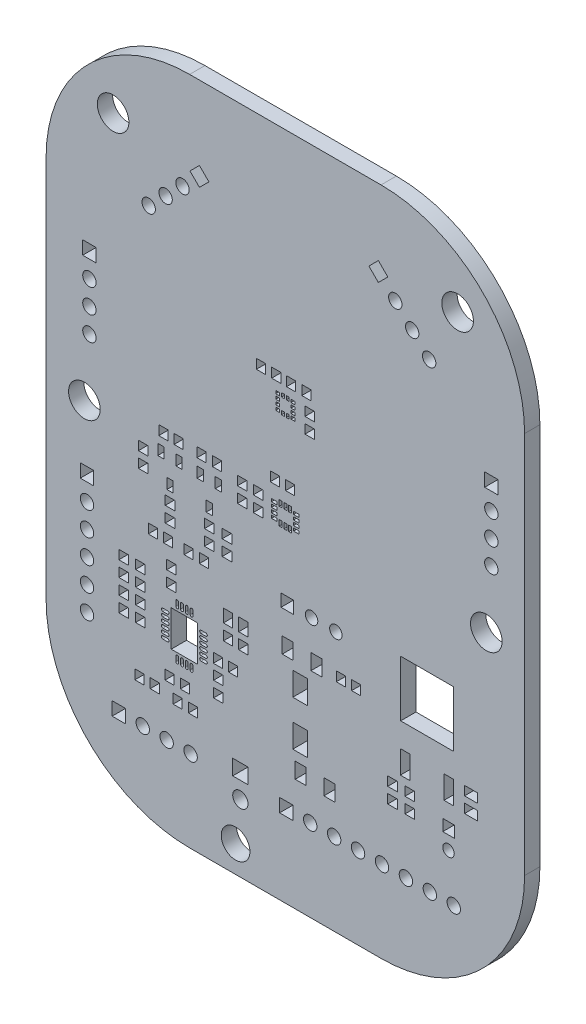
SolidWorks part; units mm, degrees
ref_plane "Plan de face" through (0, 0, 0) normal (0, 0, 1) x (1, 0, 0)
ref_plane "Plan de dessus" through (0, 0, 0) normal (0, 1, 0) x (1, 0, 0)
ref_plane "Plan de droite" through (0, 0, 0) normal (1, 0, 0) x (0, 0, -1)
sketch "Model" plane through (0, 0, 0) normal (0, 0, 1) x (1, 0, 0)
  line L0 (26, 44.4) -> (26, 44.1)
  line L1 (26, 44.1) -> (25.6, 44.1)
  line L2 (25.6, 44.1) -> (25.6, 44.4)
  line L3 (25.6, 44.4) -> (26, 44.4)
  line L4 (26, 44.9) -> (26, 44.6)
  line L5 (26, 44.6) -> (25.6, 44.6)
  line L6 (25.6, 44.6) -> (25.6, 44.9)
  line L7 (25.6, 44.9) -> (26, 44.9)
  line L8 (26, 45.4) -> (26, 45.1)
  line L9 (26, 45.1) -> (25.6, 45.1)
  line L10 (25.6, 45.1) -> (25.6, 45.4)
  line L11 (25.6, 45.4) -> (26, 45.4)
  line L12 (26, 45.9) -> (26, 45.6)
  line L13 (26, 45.6) -> (25.6, 45.6)
  line L14 (25.6, 45.6) -> (25.6, 45.9)
  line L15 (25.6, 45.9) -> (26, 45.9)
  line L16 (25.1, 46) -> (25.4, 46)
  line L17 (25.4, 46) -> (25.4, 45.6)
  line L18 (25.4, 45.6) -> (25.1, 45.6)
  line L19 (25.1, 45.6) -> (25.1, 46)
  line L20 (24.6, 46) -> (24.9, 46)
  line L21 (24.9, 46) -> (24.9, 45.6)
  line L22 (24.9, 45.6) -> (24.6, 45.6)
  line L23 (24.6, 45.6) -> (24.6, 46)
  line L24 (24.4, 45.9) -> (24.4, 45.6)
  line L25 (24.4, 45.6) -> (24, 45.6)
  line L26 (24, 45.6) -> (24, 45.9)
  line L27 (24, 45.9) -> (24.4, 45.9)
  line L28 (24.4, 45.4) -> (24.4, 45.1)
  line L29 (24.4, 45.1) -> (24, 45.1)
  line L30 (24, 45.1) -> (24, 45.4)
  line L31 (24, 45.4) -> (24.4, 45.4)
  line L32 (24.4, 44.9) -> (24.4, 44.6)
  line L33 (24.4, 44.6) -> (24, 44.6)
  line L34 (24, 44.6) -> (24, 44.9)
  line L35 (24, 44.9) -> (24.4, 44.9)
  line L36 (24.4, 44.4) -> (24.4, 44.1)
  line L37 (24.4, 44.1) -> (24, 44.1)
  line L38 (24, 44.1) -> (24, 44.4)
  line L39 (24, 44.4) -> (24.4, 44.4)
  line L40 (24.6, 44.4) -> (24.9, 44.4)
  line L41 (24.9, 44.4) -> (24.9, 44)
  line L42 (24.9, 44) -> (24.6, 44)
  line L43 (24.6, 44) -> (24.6, 44.4)
  line L44 (25.1, 44.4) -> (25.4, 44.4)
  line L45 (25.4, 44.4) -> (25.4, 44)
  line L46 (25.4, 44) -> (25.1, 44)
  line L47 (25.1, 44) -> (25.1, 44.4)
  line L48 (26.45, 34.4) -> (26.45, 34.1)
  line L49 (26.45, 34.1) -> (25.85, 34.1)
  line L50 (25.85, 34.1) -> (25.85, 34.4)
  line L51 (25.85, 34.4) -> (26.45, 34.4)
  line L52 (26.45, 34.9) -> (26.45, 34.6)
  line L53 (26.45, 34.6) -> (25.85, 34.6)
  line L54 (25.85, 34.6) -> (25.85, 34.9)
  line L55 (25.85, 34.9) -> (26.45, 34.9)
  line L56 (26.45, 35.4) -> (26.45, 35.1)
  line L57 (26.45, 35.1) -> (25.85, 35.1)
  line L58 (25.85, 35.1) -> (25.85, 35.4)
  line L59 (25.85, 35.4) -> (26.45, 35.4)
  line L60 (26.45, 35.9) -> (26.45, 35.6)
  line L61 (26.45, 35.6) -> (25.85, 35.6)
  line L62 (25.85, 35.6) -> (25.85, 35.9)
  line L63 (25.85, 35.9) -> (26.45, 35.9)
  line L64 (25.35, 36.2) -> (25.65, 36.2)
  line L65 (25.65, 36.2) -> (25.65, 35.6)
  line L66 (25.65, 35.6) -> (25.35, 35.6)
  line L67 (25.35, 35.6) -> (25.35, 36.2)
  line L68 (24.85, 36.2) -> (25.15, 36.2)
  line L69 (25.15, 36.2) -> (25.15, 35.6)
  line L70 (25.15, 35.6) -> (24.85, 35.6)
  line L71 (24.85, 35.6) -> (24.85, 36.2)
  line L72 (24.35, 36.2) -> (24.65, 36.2)
  line L73 (24.65, 36.2) -> (24.65, 35.6)
  line L74 (24.65, 35.6) -> (24.35, 35.6)
  line L75 (24.35, 35.6) -> (24.35, 36.2)
  line L76 (24.15, 35.9) -> (24.15, 35.6)
  line L77 (24.15, 35.6) -> (23.55, 35.6)
  line L78 (23.55, 35.6) -> (23.55, 35.9)
  line L79 (23.55, 35.9) -> (24.15, 35.9)
  line L80 (24.15, 35.4) -> (24.15, 35.1)
  line L81 (24.15, 35.1) -> (23.55, 35.1)
  line L82 (23.55, 35.1) -> (23.55, 35.4)
  line L83 (23.55, 35.4) -> (24.15, 35.4)
  line L84 (24.15, 34.9) -> (24.15, 34.6)
  line L85 (24.15, 34.6) -> (23.55, 34.6)
  line L86 (23.55, 34.6) -> (23.55, 34.9)
  line L87 (23.55, 34.9) -> (24.15, 34.9)
  line L88 (24.15, 34.4) -> (24.15, 34.1)
  line L89 (24.15, 34.1) -> (23.55, 34.1)
  line L90 (23.55, 34.1) -> (23.55, 34.4)
  line L91 (23.55, 34.4) -> (24.15, 34.4)
  line L92 (24.35, 34.4) -> (24.65, 34.4)
  line L93 (24.65, 34.4) -> (24.65, 33.8)
  line L94 (24.65, 33.8) -> (24.35, 33.8)
  line L95 (24.35, 33.8) -> (24.35, 34.4)
  line L96 (24.85, 34.4) -> (25.15, 34.4)
  line L97 (25.15, 34.4) -> (25.15, 33.8)
  line L98 (25.15, 33.8) -> (24.85, 33.8)
  line L99 (24.85, 33.8) -> (24.85, 34.4)
  line L100 (25.35, 34.4) -> (25.65, 34.4)
  line L101 (25.65, 34.4) -> (25.65, 33.8)
  line L102 (25.65, 33.8) -> (25.35, 33.8)
  line L103 (25.35, 33.8) -> (25.35, 34.4)
  line L104 (20.125, 23.475) -> (21.075, 23.475)
  line L105 (21.075, 23.475) -> (21.075, 22.125)
  line L106 (21.075, 22.125) -> (20.125, 22.125)
  line L107 (20.125, 22.125) -> (20.125, 23.475)
  line L108 (18.525, 23.475) -> (19.475, 23.475)
  line L109 (19.475, 23.475) -> (19.475, 22.125)
  line L110 (19.475, 22.125) -> (18.525, 22.125)
  line L111 (18.525, 22.125) -> (18.525, 23.475)
  line L112 (16.2, 17.8) -> (16.7, 17.8)
  line L113 (16.7, 17.5) -> (16.2, 17.5)
  line L114 (16.2, 18.3) -> (16.7, 18.3)
  line L115 (16.7, 18) -> (16.2, 18)
  line L116 (16.2, 18.8) -> (16.7, 18.8)
  line L117 (16.7, 18.5) -> (16.2, 18.5)
  line L118 (16.2, 19.3) -> (16.7, 19.3)
  line L119 (16.7, 19) -> (16.2, 19)
  line L120 (16.2, 19.8) -> (16.7, 19.8)
  line L121 (16.7, 19.5) -> (16.2, 19.5)
  line L122 (16.2, 20.3) -> (16.7, 20.3)
  line L123 (16.7, 20) -> (16.2, 20)
  line L124 (15.05, 21.15) -> (15.05, 21.65)
  line L125 (15.35, 21.65) -> (15.35, 21.15)
  line L126 (14.55, 21.15) -> (14.55, 21.65)
  line L127 (14.85, 21.65) -> (14.85, 21.15)
  line L128 (14.05, 21.15) -> (14.05, 21.65)
  line L129 (14.35, 21.65) -> (14.35, 21.15)
  line L130 (13.55, 21.15) -> (13.55, 21.65)
  line L131 (13.85, 21.65) -> (13.85, 21.15)
  line L132 (12.2, 20.3) -> (12.7, 20.3)
  line L133 (12.7, 20) -> (12.2, 20)
  line L134 (12.2, 19.8) -> (12.7, 19.8)
  line L135 (12.7, 19.5) -> (12.2, 19.5)
  line L136 (12.2, 19.3) -> (12.7, 19.3)
  line L137 (12.7, 19) -> (12.2, 19)
  line L138 (12.2, 18.8) -> (12.7, 18.8)
  line L139 (12.7, 18.5) -> (12.2, 18.5)
  line L140 (12.2, 18.3) -> (12.7, 18.3)
  line L141 (12.7, 18) -> (12.2, 18)
  line L142 (12.2, 17.8) -> (12.7, 17.8)
  line L143 (12.7, 17.5) -> (12.2, 17.5)
  line L144 (13.55, 16.15) -> (13.55, 16.65)
  line L145 (13.85, 16.65) -> (13.85, 16.15)
  line L146 (14.05, 16.15) -> (14.05, 16.65)
  line L147 (14.35, 16.65) -> (14.35, 16.15)
  line L148 (14.55, 16.15) -> (14.55, 16.65)
  line L149 (14.85, 16.65) -> (14.85, 16.15)
  line L150 (15.05, 16.15) -> (15.05, 16.65)
  line L151 (15.35, 16.65) -> (15.35, 16.15)
  line L152 (15.825, 20.775) -> (15.825, 17.025)
  line L153 (15.825, 17.025) -> (13.075, 17.025)
  line L154 (13.075, 17.025) -> (13.075, 20.775)
  line L155 (13.075, 20.775) -> (15.825, 20.775)
  line L156 (13.575, 34.95) -> (14.225, 34.95)
  line L157 (14.225, 34.95) -> (14.225, 33.85)
  line L158 (14.225, 33.85) -> (13.575, 33.85)
  line L159 (13.575, 33.85) -> (13.575, 34.95)
  line L160 (11.675, 34.95) -> (12.325, 34.95)
  line L161 (12.325, 34.95) -> (12.325, 33.85)
  line L162 (12.325, 33.85) -> (11.675, 33.85)
  line L163 (11.675, 33.85) -> (11.675, 34.95)
  line L164 (12.625, 32.35) -> (13.275, 32.35)
  line L165 (13.275, 32.35) -> (13.275, 31.25)
  line L166 (13.275, 31.25) -> (12.625, 31.25)
  line L167 (12.625, 31.25) -> (12.625, 32.35)
  line L168 (17.675, 34.95) -> (18.325, 34.95)
  line L169 (18.325, 34.95) -> (18.325, 33.85)
  line L170 (18.325, 33.85) -> (17.675, 33.85)
  line L171 (17.675, 33.85) -> (17.675, 34.95)
  line L172 (15.775, 34.95) -> (16.425, 34.95)
  line L173 (16.425, 34.95) -> (16.425, 33.85)
  line L174 (16.425, 33.85) -> (15.775, 33.85)
  line L175 (15.775, 33.85) -> (15.775, 34.95)
  line L176 (16.725, 32.35) -> (17.375, 32.35)
  line L177 (17.375, 32.35) -> (17.375, 31.25)
  line L178 (17.375, 31.25) -> (16.725, 31.25)
  line L179 (16.725, 31.25) -> (16.725, 32.35)
  line L180 (43.725, 19.075) -> (43.725, 20.025)
  line L181 (43.725, 20.025) -> (45.075, 20.025)
  line L182 (45.075, 20.025) -> (45.075, 19.075)
  line L183 (45.075, 19.075) -> (43.725, 19.075)
  line L184 (43.725, 17.475) -> (43.725, 18.425)
  line L185 (43.725, 18.425) -> (45.075, 18.425)
  line L186 (45.075, 18.425) -> (45.075, 17.475)
  line L187 (45.075, 17.475) -> (43.725, 17.475)
  line L188 (41.45, 15.9) -> (42.65, 15.9)
  line L189 (42.65, 15.9) -> (42.65, 14.7)
  line L190 (42.65, 14.7) -> (41.45, 14.7)
  line L191 (41.45, 14.7) -> (41.45, 15.9)
  line L192 (41.45, 15.9) -> (42.65, 15.9)
  line L193 (42.65, 15.9) -> (42.65, 14.7)
  line L194 (42.65, 14.7) -> (41.45, 14.7)
  line L195 (41.45, 14.7) -> (41.45, 15.9)
  line L196 (38.02, 17.6) -> (37.02, 17.6)
  line L197 (37.02, 17.6) -> (37.02, 20)
  line L198 (37.02, 20) -> (38.02, 20)
  line L199 (38.02, 20) -> (38.02, 17.6)
  line L200 (42.58, 17.6) -> (41.58, 17.6)
  line L201 (41.58, 17.6) -> (41.58, 20)
  line L202 (41.58, 20) -> (42.58, 20)
  line L203 (42.58, 20) -> (42.58, 17.6)
  line L204 (42.55, 22.525) -> (37.05, 22.525)
  line L205 (37.05, 22.525) -> (37.05, 28.375)
  line L206 (37.05, 28.375) -> (42.55, 28.375)
  line L207 (42.55, 28.375) -> (42.55, 22.525)
  line L208 (37.5, 15.925) -> (37.5, 16.875)
  line L209 (37.5, 16.875) -> (38.5, 16.875)
  line L210 (38.5, 16.875) -> (38.5, 15.925)
  line L211 (38.5, 15.925) -> (37.5, 15.925)
  line L212 (37.5, 14.325) -> (37.5, 15.275)
  line L213 (37.5, 15.275) -> (38.5, 15.275)
  line L214 (38.5, 15.275) -> (38.5, 14.325)
  line L215 (38.5, 14.325) -> (37.5, 14.325)
  line L216 (22.925, 46.8) -> (21.975, 46.8)
  line L217 (21.975, 46.8) -> (21.975, 47.8)
  line L218 (21.975, 47.8) -> (22.925, 47.8)
  line L219 (22.925, 47.8) -> (22.925, 46.8)
  line L220 (24.525, 46.8) -> (23.575, 46.8)
  line L221 (23.575, 46.8) -> (23.575, 47.8)
  line L222 (23.575, 47.8) -> (24.525, 47.8)
  line L223 (24.525, 47.8) -> (24.525, 46.8)
  line L224 (26.725, 47.8) -> (27.675, 47.8)
  line L225 (27.675, 47.8) -> (27.675, 46.8)
  line L226 (27.675, 46.8) -> (26.725, 46.8)
  line L227 (26.725, 46.8) -> (26.725, 47.8)
  line L228 (25.125, 47.8) -> (26.075, 47.8)
  line L229 (26.075, 47.8) -> (26.075, 46.8)
  line L230 (26.075, 46.8) -> (25.125, 46.8)
  line L231 (25.125, 46.8) -> (25.125, 47.8)
  line L232 (28.05, 44.425) -> (28.05, 43.475)
  line L233 (28.05, 43.475) -> (27.05, 43.475)
  line L234 (27.05, 43.475) -> (27.05, 44.425)
  line L235 (27.05, 44.425) -> (28.05, 44.425)
  line L236 (28.05, 46.025) -> (28.05, 45.075)
  line L237 (28.05, 45.075) -> (27.05, 45.075)
  line L238 (27.05, 45.075) -> (27.05, 46.025)
  line L239 (27.05, 46.025) -> (28.05, 46.025)
  line L240 (24.375, 37.35) -> (23.425, 37.35)
  line L241 (23.425, 37.35) -> (23.425, 38.35)
  line L242 (23.425, 38.35) -> (24.375, 38.35)
  line L243 (24.375, 38.35) -> (24.375, 37.35)
  line L244 (25.975, 37.35) -> (25.025, 37.35)
  line L245 (25.025, 37.35) -> (25.025, 38.35)
  line L246 (25.025, 38.35) -> (25.975, 38.35)
  line L247 (25.975, 38.35) -> (25.975, 37.35)
  line L248 (21, 34.625) -> (21, 33.675)
  line L249 (21, 33.675) -> (20, 33.675)
  line L250 (20, 33.675) -> (20, 34.625)
  line L251 (20, 34.625) -> (21, 34.625)
  line L252 (21, 36.225) -> (21, 35.275)
  line L253 (21, 35.275) -> (20, 35.275)
  line L254 (20, 35.275) -> (20, 36.225)
  line L255 (20, 36.225) -> (21, 36.225)
  line L256 (22.65, 34.625) -> (22.65, 33.675)
  line L257 (22.65, 33.675) -> (21.65, 33.675)
  line L258 (21.65, 33.675) -> (21.65, 34.625)
  line L259 (21.65, 34.625) -> (22.65, 34.625)
  line L260 (22.65, 36.225) -> (22.65, 35.275)
  line L261 (22.65, 35.275) -> (21.65, 35.275)
  line L262 (21.65, 35.275) -> (21.65, 36.225)
  line L263 (21.65, 36.225) -> (22.65, 36.225)
  line L264 (19.475, 20.5) -> (18.525, 20.5)
  line L265 (18.525, 20.5) -> (18.525, 21.5)
  line L266 (18.525, 21.5) -> (19.475, 21.5)
  line L267 (19.475, 21.5) -> (19.475, 20.5)
  line L268 (21.075, 20.5) -> (20.125, 20.5)
  line L269 (20.125, 20.5) -> (20.125, 21.5)
  line L270 (20.125, 21.5) -> (21.075, 21.5)
  line L271 (21.075, 21.5) -> (21.075, 20.5)
  line L272 (14.025, 14.9) -> (14.975, 14.9)
  line L273 (14.975, 14.9) -> (14.975, 13.9)
  line L274 (14.975, 13.9) -> (14.025, 13.9)
  line L275 (14.025, 13.9) -> (14.025, 14.9)
  line L276 (12.425, 14.9) -> (13.375, 14.9)
  line L277 (13.375, 14.9) -> (13.375, 13.9)
  line L278 (13.375, 13.9) -> (12.425, 13.9)
  line L279 (12.425, 13.9) -> (12.425, 14.9)
  line L280 (10.875, 13.35) -> (11.825, 13.35)
  line L281 (11.825, 13.35) -> (11.825, 12.35)
  line L282 (11.825, 12.35) -> (10.875, 12.35)
  line L283 (10.875, 12.35) -> (10.875, 13.35)
  line L284 (9.275, 13.35) -> (10.225, 13.35)
  line L285 (10.225, 13.35) -> (10.225, 12.35)
  line L286 (10.225, 12.35) -> (9.275, 12.35)
  line L287 (9.275, 12.35) -> (9.275, 13.35)
  line L288 (12.6, 23.975) -> (12.6, 24.925)
  line L289 (12.6, 24.925) -> (13.6, 24.925)
  line L290 (13.6, 24.925) -> (13.6, 23.975)
  line L291 (13.6, 23.975) -> (12.6, 23.975)
  line L292 (12.6, 22.375) -> (12.6, 23.325)
  line L293 (12.6, 23.325) -> (13.6, 23.325)
  line L294 (13.6, 23.325) -> (13.6, 22.375)
  line L295 (13.6, 22.375) -> (12.6, 22.375)
  line L296 (19.075, 18.95) -> (20.025, 18.95)
  line L297 (20.025, 18.95) -> (20.025, 17.95)
  line L298 (20.025, 17.95) -> (19.075, 17.95)
  line L299 (19.075, 17.95) -> (19.075, 18.95)
  line L300 (17.475, 18.95) -> (18.425, 18.95)
  line L301 (18.425, 18.95) -> (18.425, 17.95)
  line L302 (18.425, 17.95) -> (17.475, 17.95)
  line L303 (17.475, 17.95) -> (17.475, 18.95)
  line L304 (18.5, 15.775) -> (18.5, 14.825)
  line L305 (18.5, 14.825) -> (17.5, 14.825)
  line L306 (17.5, 14.825) -> (17.5, 15.775)
  line L307 (17.5, 15.775) -> (18.5, 15.775)
  line L308 (18.5, 17.375) -> (18.5, 16.425)
  line L309 (18.5, 16.425) -> (17.5, 16.425)
  line L310 (17.5, 16.425) -> (17.5, 17.375)
  line L311 (17.5, 17.375) -> (18.5, 17.375)
  line L312 (14.875, 13.15) -> (15.825, 13.15)
  line L313 (15.825, 13.15) -> (15.825, 12.15)
  line L314 (15.825, 12.15) -> (14.875, 12.15)
  line L315 (14.875, 12.15) -> (14.875, 13.15)
  line L316 (13.275, 13.15) -> (14.225, 13.15)
  line L317 (14.225, 13.15) -> (14.225, 12.15)
  line L318 (14.225, 12.15) -> (13.275, 12.15)
  line L319 (13.275, 12.15) -> (13.275, 13.15)
  line L320 (8.6, 18.525) -> (8.6, 17.575)
  line L321 (8.6, 17.575) -> (7.6, 17.575)
  line L322 (7.6, 17.575) -> (7.6, 18.525)
  line L323 (7.6, 18.525) -> (8.6, 18.525)
  line L324 (8.6, 20.125) -> (8.6, 19.175)
  line L325 (8.6, 19.175) -> (7.6, 19.175)
  line L326 (7.6, 19.175) -> (7.6, 20.125)
  line L327 (7.6, 20.125) -> (8.6, 20.125)
  line L328 (10.35, 18.525) -> (10.35, 17.575)
  line L329 (10.35, 17.575) -> (9.35, 17.575)
  line L330 (9.35, 17.575) -> (9.35, 18.525)
  line L331 (9.35, 18.525) -> (10.35, 18.525)
  line L332 (10.35, 20.125) -> (10.35, 19.175)
  line L333 (10.35, 19.175) -> (9.35, 19.175)
  line L334 (9.35, 19.175) -> (9.35, 20.125)
  line L335 (9.35, 20.125) -> (10.35, 20.125)
  line L336 (8.6, 21.725) -> (8.6, 20.775)
  line L337 (8.6, 20.775) -> (7.6, 20.775)
  line L338 (7.6, 20.775) -> (7.6, 21.725)
  line L339 (7.6, 21.725) -> (8.6, 21.725)
  line L340 (8.6, 23.325) -> (8.6, 22.375)
  line L341 (8.6, 22.375) -> (7.6, 22.375)
  line L342 (7.6, 22.375) -> (7.6, 23.325)
  line L343 (7.6, 23.325) -> (8.6, 23.325)
  line L344 (10.35, 21.725) -> (10.35, 20.775)
  line L345 (10.35, 20.775) -> (9.35, 20.775)
  line L346 (9.35, 20.775) -> (9.35, 21.725)
  line L347 (9.35, 21.725) -> (10.35, 21.725)
  line L348 (10.35, 23.325) -> (10.35, 22.375)
  line L349 (10.35, 22.375) -> (9.35, 22.375)
  line L350 (9.35, 22.375) -> (9.35, 23.325)
  line L351 (9.35, 23.325) -> (10.35, 23.325)
  line L352 (15.375, 26.25) -> (14.425, 26.25)
  line L353 (14.425, 26.25) -> (14.425, 27.25)
  line L354 (14.425, 27.25) -> (15.375, 27.25)
  line L355 (15.375, 27.25) -> (15.375, 26.25)
  line L356 (16.975, 26.25) -> (16.025, 26.25)
  line L357 (16.025, 26.25) -> (16.025, 27.25)
  line L358 (16.025, 27.25) -> (16.975, 27.25)
  line L359 (16.975, 27.25) -> (16.975, 26.25)
  line L360 (11.625, 26.25) -> (10.675, 26.25)
  line L361 (10.675, 26.25) -> (10.675, 27.25)
  line L362 (10.675, 27.25) -> (11.625, 27.25)
  line L363 (11.625, 27.25) -> (11.625, 26.25)
  line L364 (13.225, 26.25) -> (12.275, 26.25)
  line L365 (12.275, 26.25) -> (12.275, 27.25)
  line L366 (12.275, 27.25) -> (13.225, 27.25)
  line L367 (13.225, 27.25) -> (13.225, 26.25)
  line L368 (10.65, 32.625) -> (10.65, 31.675)
  line L369 (10.65, 31.675) -> (9.65, 31.675)
  line L370 (9.65, 31.675) -> (9.65, 32.625)
  line L371 (9.65, 32.625) -> (10.65, 32.625)
  line L372 (10.65, 34.225) -> (10.65, 33.275)
  line L373 (10.65, 33.275) -> (9.65, 33.275)
  line L374 (9.65, 33.275) -> (9.65, 34.225)
  line L375 (9.65, 34.225) -> (10.65, 34.225)
  line L376 (13.375, 36.7) -> (14.325, 36.7)
  line L377 (14.325, 36.7) -> (14.325, 35.7)
  line L378 (14.325, 35.7) -> (13.375, 35.7)
  line L379 (13.375, 35.7) -> (13.375, 36.7)
  line L380 (11.775, 36.7) -> (12.725, 36.7)
  line L381 (12.725, 36.7) -> (12.725, 35.7)
  line L382 (12.725, 35.7) -> (11.775, 35.7)
  line L383 (11.775, 35.7) -> (11.775, 36.7)
  line L384 (13.45, 29.075) -> (13.45, 28.125)
  line L385 (13.45, 28.125) -> (12.45, 28.125)
  line L386 (12.45, 28.125) -> (12.45, 29.075)
  line L387 (12.45, 29.075) -> (13.45, 29.075)
  line L388 (13.45, 30.675) -> (13.45, 29.725)
  line L389 (13.45, 29.725) -> (12.45, 29.725)
  line L390 (12.45, 29.725) -> (12.45, 30.675)
  line L391 (12.45, 30.675) -> (13.45, 30.675)
  line L392 (17.375, 36.7) -> (18.325, 36.7)
  line L393 (18.325, 36.7) -> (18.325, 35.7)
  line L394 (18.325, 35.7) -> (17.375, 35.7)
  line L395 (17.375, 35.7) -> (17.375, 36.7)
  line L396 (15.775, 36.7) -> (16.725, 36.7)
  line L397 (16.725, 36.7) -> (16.725, 35.7)
  line L398 (16.725, 35.7) -> (15.775, 35.7)
  line L399 (15.775, 35.7) -> (15.775, 36.7)
  line L400 (17.55, 29.025) -> (17.55, 28.075)
  line L401 (17.55, 28.075) -> (16.55, 28.075)
  line L402 (16.55, 28.075) -> (16.55, 29.025)
  line L403 (16.55, 29.025) -> (17.55, 29.025)
  line L404 (17.55, 30.625) -> (17.55, 29.675)
  line L405 (17.55, 29.675) -> (16.55, 29.675)
  line L406 (16.55, 29.675) -> (16.55, 30.625)
  line L407 (16.55, 30.625) -> (17.55, 30.625)
  line L408 (36.7, 15.275) -> (36.7, 14.325)
  line L409 (36.7, 14.325) -> (35.7, 14.325)
  line L410 (35.7, 14.325) -> (35.7, 15.275)
  line L411 (35.7, 15.275) -> (36.7, 15.275)
  line L412 (36.7, 16.875) -> (36.7, 15.925)
  line L413 (36.7, 15.925) -> (35.7, 15.925)
  line L414 (35.7, 15.925) -> (35.7, 16.875)
  line L415 (35.7, 16.875) -> (36.7, 16.875)
  line L416 (31.275, 22.7) -> (30.325, 22.7)
  line L417 (30.325, 22.7) -> (30.325, 23.7)
  line L418 (30.325, 23.7) -> (31.275, 23.7)
  line L419 (31.275, 23.7) -> (31.275, 22.7)
  line L420 (32.875, 22.7) -> (31.925, 22.7)
  line L421 (31.925, 22.7) -> (31.925, 23.7)
  line L422 (31.925, 23.7) -> (32.875, 23.7)
  line L423 (32.875, 23.7) -> (32.875, 22.7)
  line L424 (19.4, 29.025) -> (19.4, 28.075)
  line L425 (19.4, 28.075) -> (18.4, 28.075)
  line L426 (18.4, 28.075) -> (18.4, 29.025)
  line L427 (18.4, 29.025) -> (19.4, 29.025)
  line L428 (19.4, 30.625) -> (19.4, 29.675)
  line L429 (19.4, 29.675) -> (18.4, 29.675)
  line L430 (18.4, 29.675) -> (18.4, 30.625)
  line L431 (18.4, 30.625) -> (19.4, 30.625)
  line L432 (27.675, 24.025) -> (28.825, 24.025)
  line L433 (28.825, 24.025) -> (28.825, 22.375)
  line L434 (28.825, 22.375) -> (27.675, 22.375)
  line L435 (27.675, 22.375) -> (27.675, 24.025)
  line L436 (24.675, 24.025) -> (25.825, 24.025)
  line L437 (25.825, 24.025) -> (25.825, 22.375)
  line L438 (25.825, 22.375) -> (24.675, 22.375)
  line L439 (24.675, 22.375) -> (24.675, 24.025)
  line L440 (29.025, 13.375) -> (30.175, 13.375)
  line L441 (30.175, 13.375) -> (30.175, 11.725)
  line L442 (30.175, 11.725) -> (29.025, 11.725)
  line L443 (29.025, 11.725) -> (29.025, 13.375)
  line L444 (26.025, 13.375) -> (27.175, 13.375)
  line L445 (27.175, 13.375) -> (27.175, 11.725)
  line L446 (27.175, 11.725) -> (26.025, 11.725)
  line L447 (26.025, 11.725) -> (26.025, 13.375)
  line L448 (27.325, 14.325) -> (25.775, 14.325)
  line L449 (25.775, 14.325) -> (25.775, 16.775)
  line L450 (25.775, 16.775) -> (27.325, 16.775)
  line L451 (27.325, 16.775) -> (27.325, 14.325)
  line L452 (27.325, 19.025) -> (25.775, 19.025)
  line L453 (25.775, 19.025) -> (25.775, 21.475)
  line L454 (25.775, 21.475) -> (27.325, 21.475)
  line L455 (27.325, 21.475) -> (27.325, 19.025)
  line L456 (45.825, 49.45) -> (47.225, 49.45)
  line L457 (47.225, 49.45) -> (47.225, 48.05)
  line L458 (47.225, 48.05) -> (45.825, 48.05)
  line L459 (45.825, 48.05) -> (45.825, 49.45)
  line L460 (45.825, 49.45) -> (47.225, 49.45)
  line L461 (47.225, 49.45) -> (47.225, 48.05)
  line L462 (47.225, 48.05) -> (45.825, 48.05)
  line L463 (45.825, 48.05) -> (45.825, 49.45)
  line L464 (33.7296, 62.0228) -> (34.7195, 63.0127)
  line L465 (34.7195, 63.0127) -> (35.7094, 62.0228)
  line L466 (35.7094, 62.0228) -> (34.7195, 61.0329)
  line L467 (34.7195, 61.0329) -> (33.7296, 62.0228)
  line L468 (33.7296, 62.0228) -> (34.7195, 63.0127)
  line L469 (34.7195, 63.0127) -> (35.7094, 62.0228)
  line L470 (35.7094, 62.0228) -> (34.7195, 61.0329)
  line L471 (34.7195, 61.0329) -> (33.7296, 62.0228)
  line L472 (16.0228, 62.2703) -> (17.0127, 61.2804)
  line L473 (17.0127, 61.2804) -> (16.0228, 60.2905)
  line L474 (16.0228, 60.2905) -> (15.0329, 61.2804)
  line L475 (15.0329, 61.2804) -> (16.0228, 62.2703)
  line L476 (16.0228, 62.2703) -> (17.0127, 61.2804)
  line L477 (17.0127, 61.2804) -> (16.0228, 60.2905)
  line L478 (16.0228, 60.2905) -> (15.0329, 61.2804)
  line L479 (15.0329, 61.2804) -> (16.0228, 62.2703)
  line L480 (3.825, 49.45) -> (5.225, 49.45)
  line L481 (5.225, 49.45) -> (5.225, 48.05)
  line L482 (5.225, 48.05) -> (3.825, 48.05)
  line L483 (3.825, 48.05) -> (3.825, 49.45)
  line L484 (3.825, 49.45) -> (5.225, 49.45)
  line L485 (5.225, 49.45) -> (5.225, 48.05)
  line L486 (5.225, 48.05) -> (3.825, 48.05)
  line L487 (3.825, 48.05) -> (3.825, 49.45)
  line L488 (6.9, 7.875) -> (6.9, 9.275)
  line L489 (6.9, 9.275) -> (8.3, 9.275)
  line L490 (8.3, 9.275) -> (8.3, 7.875)
  line L491 (8.3, 7.875) -> (6.9, 7.875)
  line L492 (6.9, 7.875) -> (6.9, 9.275)
  line L493 (6.9, 9.275) -> (8.3, 9.275)
  line L494 (8.3, 9.275) -> (8.3, 7.875)
  line L495 (8.3, 7.875) -> (6.9, 7.875)
  line L496 (19.5, 10.37) -> (21.1, 10.37)
  line L497 (21.1, 10.37) -> (21.1, 8.77)
  line L498 (21.1, 8.77) -> (19.5, 8.77)
  line L499 (19.5, 8.77) -> (19.5, 10.37)
  line L500 (19.5, 10.37) -> (21.1, 10.37)
  line L501 (21.1, 10.37) -> (21.1, 8.77)
  line L502 (21.1, 8.77) -> (19.5, 8.77)
  line L503 (19.5, 8.77) -> (19.5, 10.37)
  line L504 (24.4, 7.875) -> (24.4, 9.275)
  line L505 (24.4, 9.275) -> (25.8, 9.275)
  line L506 (25.8, 9.275) -> (25.8, 7.875)
  line L507 (25.8, 7.875) -> (24.4, 7.875)
  line L508 (24.4, 7.875) -> (24.4, 9.275)
  line L509 (24.4, 9.275) -> (25.8, 9.275)
  line L510 (25.8, 9.275) -> (25.8, 7.875)
  line L511 (25.8, 7.875) -> (24.4, 7.875)
  line L512 (3.575, 29.15) -> (4.975, 29.15)
  line L513 (4.975, 29.15) -> (4.975, 27.75)
  line L514 (4.975, 27.75) -> (3.575, 27.75)
  line L515 (3.575, 27.75) -> (3.575, 29.15)
  line L516 (3.575, 29.15) -> (4.975, 29.15)
  line L517 (4.975, 29.15) -> (4.975, 27.75)
  line L518 (4.975, 27.75) -> (3.575, 27.75)
  line L519 (3.575, 27.75) -> (3.575, 29.15)
  line L520 (24.55, 26.55) -> (24.55, 27.85)
  line L521 (24.55, 27.85) -> (25.85, 27.85)
  line L522 (25.85, 27.85) -> (25.85, 26.55)
  line L523 (25.85, 26.55) -> (24.55, 26.55)
  line L524 (24.55, 26.55) -> (24.55, 27.85)
  line L525 (24.55, 27.85) -> (25.85, 27.85)
  line L526 (25.85, 27.85) -> (25.85, 26.55)
  line L527 (25.85, 26.55) -> (24.55, 26.55)
  line L528 (15, 0) -> (35, 0)
  line L529 (50, 15) -> (50, 55)
  line L530 (35, 70) -> (15, 70)
  line L531 (0, 55) -> (0, 15)
  circle A0 centre (4, 35) radius 1.651
  circle A1 centre (4, 35) radius 1.651
  circle A2 centre (7, 62.5) radius 1.651
  circle A3 centre (7, 62.5) radius 1.651
  circle A4 centre (46, 35) radius 1.651
  circle A5 centre (46, 35) radius 1.651
  circle A6 centre (43, 62.5) radius 1.651
  circle A7 centre (43, 62.5) radius 1.651
  circle A8 centre (42.05, 13.3) radius 0.6
  circle A9 centre (42.05, 13.3) radius 0.6
  circle A10 centre (19.8, 2.8) radius 1.5
  circle A11 centre (19.8, 2.8) radius 1.5
  circle A12 centre (46.525, 46.25) radius 0.7
  circle A13 centre (46.525, 46.25) radius 0.7
  circle A14 centre (46.525, 43.75) radius 0.7
  circle A15 centre (46.525, 43.75) radius 0.7
  circle A16 centre (46.525, 41.25) radius 0.7
  circle A17 centre (46.525, 41.25) radius 0.7
  circle A18 centre (36.4873, 60.255) radius 0.7
  circle A19 centre (36.4873, 60.255) radius 0.7
  circle A20 centre (38.255, 58.4873) radius 0.7
  circle A21 centre (38.255, 58.4873) radius 0.7
  circle A22 centre (40.0228, 56.7195) radius 0.7
  circle A23 centre (40.0228, 56.7195) radius 0.7
  circle A24 centre (14.255, 59.5126) radius 0.7
  circle A25 centre (14.255, 59.5126) radius 0.7
  circle A26 centre (12.4873, 57.7449) radius 0.7
  circle A27 centre (12.4873, 57.7449) radius 0.7
  circle A28 centre (10.7195, 55.9771) radius 0.7
  circle A29 centre (10.7195, 55.9771) radius 0.7
  circle A30 centre (4.525, 46.25) radius 0.7
  circle A31 centre (4.525, 46.25) radius 0.7
  circle A32 centre (4.525, 43.75) radius 0.7
  circle A33 centre (4.525, 43.75) radius 0.7
  circle A34 centre (4.525, 41.25) radius 0.7
  circle A35 centre (4.525, 41.25) radius 0.7
  circle A36 centre (10.1, 8.575) radius 0.7
  circle A37 centre (10.1, 8.575) radius 0.7
  circle A38 centre (12.6, 8.575) radius 0.7
  circle A39 centre (12.6, 8.575) radius 0.7
  circle A40 centre (15.1, 8.575) radius 0.7
  circle A41 centre (15.1, 8.575) radius 0.7
  circle A42 centre (20.3, 7.03) radius 0.8
  circle A43 centre (20.3, 7.03) radius 0.8
  circle A44 centre (27.6, 8.575) radius 0.7
  circle A45 centre (27.6, 8.575) radius 0.7
  circle A46 centre (30.1, 8.575) radius 0.7
  circle A47 centre (30.1, 8.575) radius 0.7
  circle A48 centre (32.6, 8.575) radius 0.7
  circle A49 centre (32.6, 8.575) radius 0.7
  circle A50 centre (35.1, 8.575) radius 0.7
  circle A51 centre (35.1, 8.575) radius 0.7
  circle A52 centre (37.6, 8.575) radius 0.7
  circle A53 centre (37.6, 8.575) radius 0.7
  circle A54 centre (40.1, 8.575) radius 0.7
  circle A55 centre (40.1, 8.575) radius 0.7
  circle A56 centre (42.6, 8.575) radius 0.7
  circle A57 centre (42.6, 8.575) radius 0.7
  circle A58 centre (4.275, 25.95) radius 0.7
  circle A59 centre (4.275, 25.95) radius 0.7
  circle A60 centre (4.275, 23.45) radius 0.7
  circle A61 centre (4.275, 23.45) radius 0.7
  circle A62 centre (4.275, 20.95) radius 0.7
  circle A63 centre (4.275, 20.95) radius 0.7
  circle A64 centre (4.275, 18.45) radius 0.7
  circle A65 centre (4.275, 18.45) radius 0.7
  circle A66 centre (4.275, 15.95) radius 0.7
  circle A67 centre (4.275, 15.95) radius 0.7
  circle A68 centre (27.74, 27.2) radius 0.65
  circle A69 centre (27.74, 27.2) radius 0.65
  circle A70 centre (30.28, 27.2) radius 0.65
  circle A71 centre (30.28, 27.2) radius 0.65
  arc A72 (16.7, 17.5) -> (16.7, 17.8) centre (16.7, 17.65) ccw
  arc A73 (16.2, 17.8) -> (16.2, 17.5) centre (16.2, 17.65) ccw
  arc A74 (16.7, 18) -> (16.7, 18.3) centre (16.7, 18.15) ccw
  arc A75 (16.2, 18.3) -> (16.2, 18) centre (16.2, 18.15) ccw
  arc A76 (16.7, 18.5) -> (16.7, 18.8) centre (16.7, 18.65) ccw
  arc A77 (16.2, 18.8) -> (16.2, 18.5) centre (16.2, 18.65) ccw
  arc A78 (16.7, 19) -> (16.7, 19.3) centre (16.7, 19.15) ccw
  arc A79 (16.2, 19.3) -> (16.2, 19) centre (16.2, 19.15) ccw
  arc A80 (16.7, 19.5) -> (16.7, 19.8) centre (16.7, 19.65) ccw
  arc A81 (16.2, 19.8) -> (16.2, 19.5) centre (16.2, 19.65) ccw
  arc A82 (16.7, 20) -> (16.7, 20.3) centre (16.7, 20.15) ccw
  arc A83 (16.2, 20.3) -> (16.2, 20) centre (16.2, 20.15) ccw
  arc A84 (15.35, 21.65) -> (15.05, 21.65) centre (15.2, 21.65) ccw
  arc A85 (15.05, 21.15) -> (15.35, 21.15) centre (15.2, 21.15) ccw
  arc A86 (14.85, 21.65) -> (14.55, 21.65) centre (14.7, 21.65) ccw
  arc A87 (14.55, 21.15) -> (14.85, 21.15) centre (14.7, 21.15) ccw
  arc A88 (14.35, 21.65) -> (14.05, 21.65) centre (14.2, 21.65) ccw
  arc A89 (14.05, 21.15) -> (14.35, 21.15) centre (14.2, 21.15) ccw
  arc A90 (13.85, 21.65) -> (13.55, 21.65) centre (13.7, 21.65) ccw
  arc A91 (13.55, 21.15) -> (13.85, 21.15) centre (13.7, 21.15) ccw
  arc A92 (12.7, 20) -> (12.7, 20.3) centre (12.7, 20.15) ccw
  arc A93 (12.2, 20.3) -> (12.2, 20) centre (12.2, 20.15) ccw
  arc A94 (12.7, 19.5) -> (12.7, 19.8) centre (12.7, 19.65) ccw
  arc A95 (12.2, 19.8) -> (12.2, 19.5) centre (12.2, 19.65) ccw
  arc A96 (12.7, 19) -> (12.7, 19.3) centre (12.7, 19.15) ccw
  arc A97 (12.2, 19.3) -> (12.2, 19) centre (12.2, 19.15) ccw
  arc A98 (12.7, 18.5) -> (12.7, 18.8) centre (12.7, 18.65) ccw
  arc A99 (12.2, 18.8) -> (12.2, 18.5) centre (12.2, 18.65) ccw
  arc A100 (12.7, 18) -> (12.7, 18.3) centre (12.7, 18.15) ccw
  arc A101 (12.2, 18.3) -> (12.2, 18) centre (12.2, 18.15) ccw
  arc A102 (12.7, 17.5) -> (12.7, 17.8) centre (12.7, 17.65) ccw
  arc A103 (12.2, 17.8) -> (12.2, 17.5) centre (12.2, 17.65) ccw
  arc A104 (13.85, 16.65) -> (13.55, 16.65) centre (13.7, 16.65) ccw
  arc A105 (13.55, 16.15) -> (13.85, 16.15) centre (13.7, 16.15) ccw
  arc A106 (14.35, 16.65) -> (14.05, 16.65) centre (14.2, 16.65) ccw
  arc A107 (14.05, 16.15) -> (14.35, 16.15) centre (14.2, 16.15) ccw
  arc A108 (14.85, 16.65) -> (14.55, 16.65) centre (14.7, 16.65) ccw
  arc A109 (14.55, 16.15) -> (14.85, 16.15) centre (14.7, 16.15) ccw
  arc A110 (15.35, 16.65) -> (15.05, 16.65) centre (15.2, 16.65) ccw
  arc A111 (15.05, 16.15) -> (15.35, 16.15) centre (15.2, 16.15) ccw
  arc A112 (35, 0) -> (50, 15) centre (35, 15) ccw
  arc A113 (50, 55) -> (35, 70) centre (35, 55) ccw
  arc A114 (15, 70) -> (0, 55) centre (15, 55) ccw
  arc A115 (0, 15) -> (15, 0) centre (15, 15) ccw
extrude "Boss.-Extru.1" add sketch "Model" along normal blind 1.6 contours L531 A115 L528 A112 L529 A113 L530 A114 L522 L523 L520 L521 L514 L515 L512 L513 L506 L507 L504 L505 L498 L499 L496 L497 L490 L491 L488 L489 L482 L483 L480 L481 L474 L475 L472 L473 L466 L467 L464 L465 L458 L459 region at (25.0381, 35.4986, 0)
